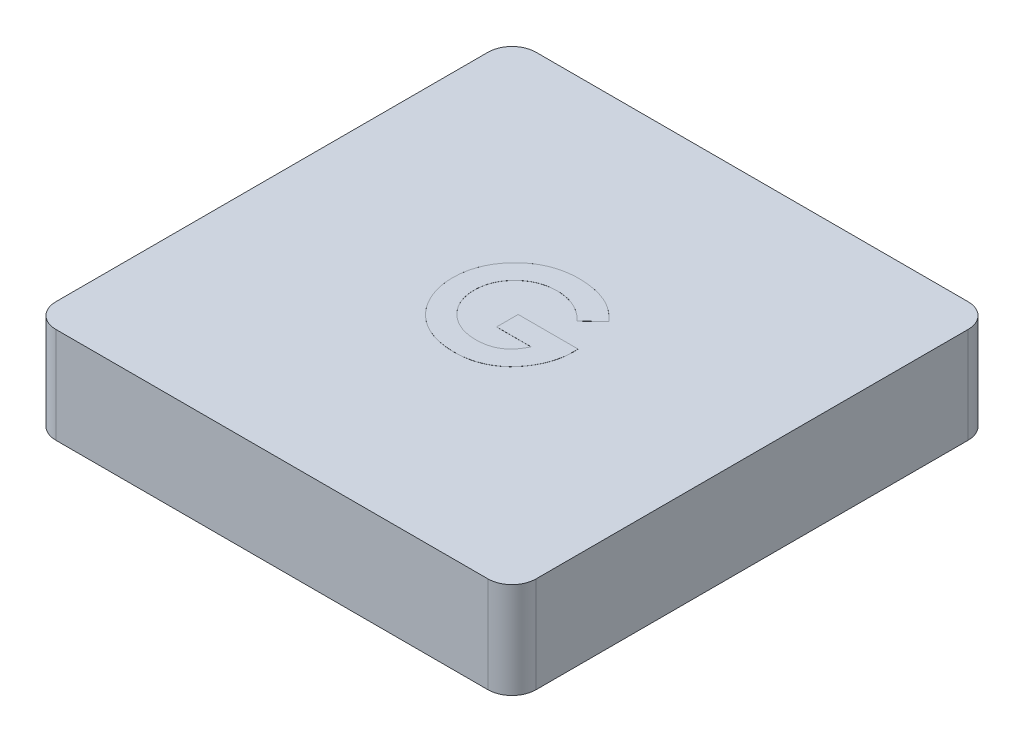
SolidWorks part; units mm, degrees
ref_plane "Front Plane" through (0, 0, 0) normal (0, 0, 1) x (1, 0, 0)
ref_plane "Top Plane" through (0, 0, 0) normal (0, 1, 0) x (1, 0, 0)
ref_plane "Right Plane" through (0, 0, 0) normal (1, 0, 0) x (0, 0, -1)
sketch "Sketch1" plane through (0, 0, 0) normal (0, 1, 0) x (1, 0, 0)
  line L0 (0, 0) -> (12.7, 0)
  line L1 (12.7, 0) -> (12.7, 12.7)
  line L2 (12.7, 12.7) -> (0, 12.7)
  line L3 (0, 12.7) -> (0, 0)
  dimension "D1" = 12.7
  dimension "D2" = 12.7
extrude "Boss-Extrude1" add sketch "Sketch1" along normal blind 2.54
fillet "Fillet1" radius 0.635 4 edges at (0, 1.27, -12.7) (12.7, 1.27, -12.7) (12.7, 1.27, 0) (0, 1.27, 0)
shell "Shell1" thickness 0.635 removed face at (6.35, 0, -6.35)
sketch "Sketch2" plane through (0, 1.905, 0) normal (0, -1, 0) x (-1, 0, 0)
  line L0 (-0.635, 6.35) -> (-12.065, 6.35) construction
  line L1 (-0.635, 12.065) -> (-0.635, 0.635) construction
  line L2 (-12.065, 0.635) -> (-12.065, 12.065) construction
  line L3 (-6.35, 0.635) -> (-6.35, 12.065) construction
  line L4 (-0.635, 0.635) -> (-12.065, 0.635) construction
  line L5 (-12.065, 12.065) -> (-0.635, 12.065) construction
  circle A0 centre (-6.35, 6.35) radius 2.54
  dimension "D1" = 5.08
extrude "Boss-Extrude2" add sketch "Sketch2" along normal up to surface (1.905 mm away) up to face at (6.35, 0, -6.35)
sketch "Sketch3" plane through (0, 2.54, 0) normal (0, 1, 0) x (1, 0, 0)
  line L0 (0, 12.065) -> (0, 0.635) construction
  line L1 (0.635, 0) -> (12.065, 0) construction
  text T0 "<b>G</b>"
  point P1 (0, 0)
  dimension "D1" = 4.4958
  dimension "D2" = 4.826
extrude "Boss-Extrude3" add sketch "Sketch3" along normal blind 0.0025
